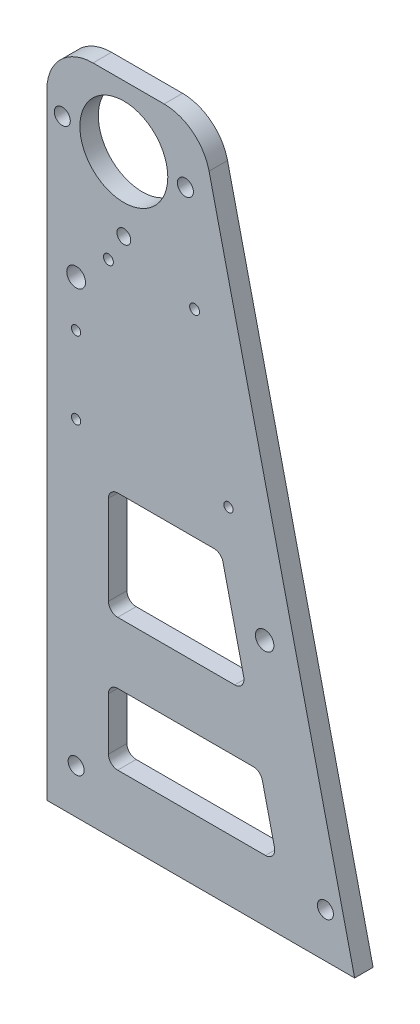
SolidWorks part; units mm, degrees
material "Policarbonato"
ref_plane "Plano frontal" through (0, 0, 0) normal (0, 0, 1) x (1, 0, 0)
ref_plane "Plano superior" through (0, 0, 0) normal (0, 1, 0) x (1, 0, 0)
ref_plane "Plano direito" through (0, 0, 0) normal (1, 0, 0) x (0, 0, -1)
sketch "Esboço1" plane through (0, 0, 0) normal (0, 0, 1) x (1, 0, 0)
  line L0 (0, 0) -> (0, 215)
  line L2 (100, 0) -> (0, 0)
  line L3 (0, 215) -> (50, 215)
  line L4 (50, 215) -> (100, 0)
  line L5 (10, 103) -> (10, 15) construction
  line L6 (25, 215) -> (25, 175) construction
  line L7 (10, 15) -> (75.7552, 15) construction
  line L8 (75.7552, 15) -> (55.2901, 103) construction
  line L9 (55.2901, 103) -> (10, 103) construction
  line L10 (20, 95) -> (20, 66)
  line L11 (23, 63) -> (61.0374, 63)
  line L12 (63.9594, 66.6795) -> (57.2152, 95.6795)
  line L13 (54.2932, 98) -> (23, 98)
  line L14 (20, 40) -> (20, 23)
  line L15 (23, 20) -> (71.0374, 20)
  line L16 (73.9594, 23.6795) -> (70.0059, 40.6795)
  line L17 (23, 43) -> (67.0839, 43)
  line L18 (0, 195) -> (50, 195) construction
  line L23 (17, 205) -> (33, 185) construction
  line L24 (17, 185) -> (33, 205) construction
  arc A8 (70.0059, 40.6795) -> (67.0839, 43) centre (67.0839, 40) ccw
  arc A9 (71.0374, 20) -> (73.9594, 23.6795) centre (71.0374, 23) ccw
  arc A10 (20, 23) -> (23, 20) centre (23, 23) ccw
  arc A11 (20, 40) -> (23, 43) centre (23, 40) cw
  arc A12 (57.2152, 95.6795) -> (54.2932, 98) centre (54.2932, 95) ccw
  arc A13 (61.0374, 63) -> (63.9594, 66.6795) centre (61.0374, 66) ccw
  arc A14 (20, 66) -> (23, 63) centre (23, 66) ccw
  arc A15 (20, 95) -> (23, 98) centre (23, 95) cw
  circle A20 centre (25, 195) radius 14.2875
  circle A21 centre (9.5, 14.5) radius 2.6
  point P8 (25, 195)
  point P49 (20, 63)
  dimension "D3" = 20
  dimension "D4" = 16
  dimension "D7" = 28.575
  dimension "D21" = 3
  dimension "D20" = 9.5
  dimension "D22" = 5.2
  dimension "D1" = 215
  dimension "D2" = 100
  dimension "D5" = 50
  dimension "D9" = 20
  dimension "D10" = 20
  dimension "D11" = 10
  dimension "D12" = 20
  dimension "D13" = 15
  dimension "D14" = 20
  dimension "D15" = 10
  dimension "D16" = 29
  dimension "D17" = 17
  dimension "D18" = 10
  dimension "D19" = 14.5
  dimension "D8" = 20
extrude "Ressalto-extrusão2" add sketch "Esboço1" along normal blind 6
fillet "Filete1" radius 15 2 edges at (0, 215, 3) (50, 215, 3)
sketch "Esboço3" plane through (0, 0, 0) normal (0, 0, -1) x (-1, 0, 0)
  line L1 (0, 0) -> (-100, 0) construction
  line L2 (0, 200) -> (0, 0) construction
  circle A0 centre (-9.5, 112) radius 1.5
  circle A1 centre (-90.5, 14.5) radius 2.6
  circle A2 centre (-9.5, 137) radius 1.5
  circle A3 centre (-9.5, 152) radius 3.05
  circle A4 centre (-59, 112) radius 1.5
  point P6 (-9.5, 112)
  point P9 (-9.5, 137)
  dimension "D5" = 5.2
  dimension "D1" = 25
  dimension "D6" = 3
  dimension "D7" = 112
  dimension "D8" = 15
  dimension "D9" = 6.1
  dimension "D10" = 49.5
  dimension "D2" = 9.5
  dimension "D3" = 14.5
  dimension "D4" = 9.5
extrude "Corte-extrusão1" cut sketch "Esboço3" against normal through all
sketch "Esboço5" plane through (0, 0, 0) normal (0, 0, -1) x (-1, 0, 0)
  line L0 (-45, 195) -> (-5, 195) construction
  circle A0 centre (-25, 171.1875) radius 2.25
  circle A1 centre (-70.7598, 80.3986) radius 3
  circle A2 centre (-25, 195) radius 14.2875 construction
  circle A3 centre (-20, 162.1875) radius 1.6
  circle A4 centre (-48, 162.1875) radius 1.6
  circle A5 centre (-45, 195) radius 2.6
  circle A6 centre (-5, 195) radius 2.6
  point P6 (-25, 195)
  point P17 (-2.4, 195)
  dimension "D1" = 23.8125
  dimension "D2" = 4.5
  dimension "D4" = 28
  dimension "D6" = 3.2
  dimension "D7" = 40
  dimension "D8" = 5.2
  dimension "D3" = 5
  dimension "D5" = 9
extrude "Corte-extrusão2" cut sketch "Esboço5" against normal through all
